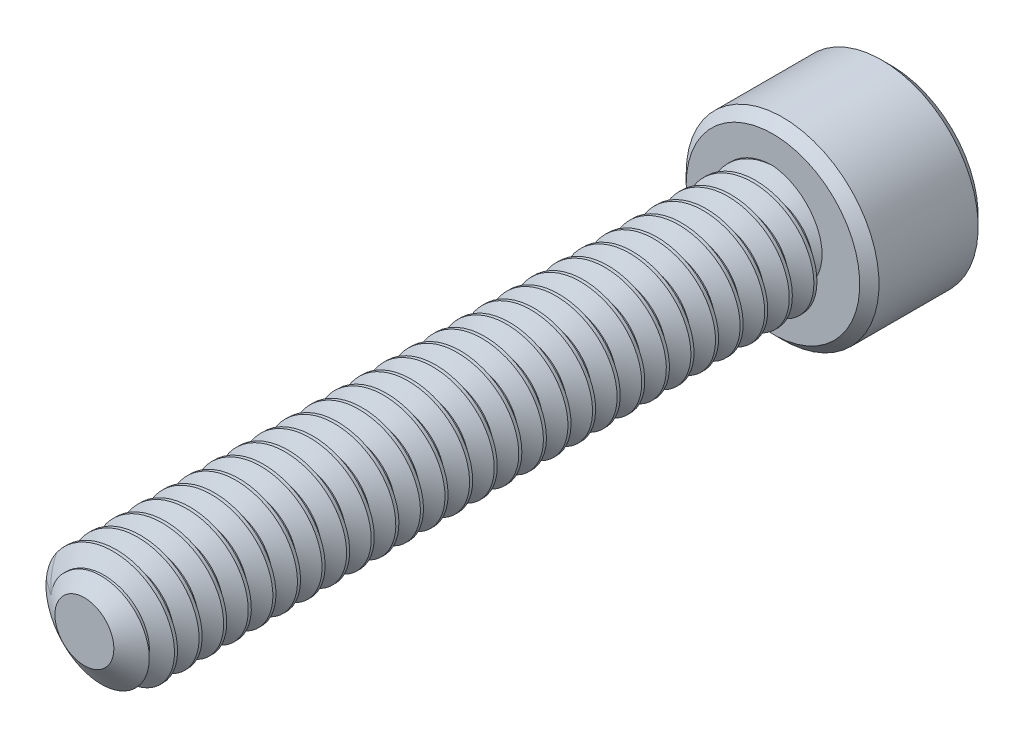
SolidWorks part; units mm, degrees
note: '?' marks a value the reader was unsure of.
other "DetailItem1"
ref_plane "Front Plane" through (0, 0, 0) normal (0, 0, 1) x (1, 0, 0)
ref_plane "Top Plane" through (0, 0, 0) normal (0, 1, 0) x (1, 0, 0)
ref_plane "Right Plane" through (0, 0, 0) normal (1, 0, 0) x (0, 0, -1)
sketch "Sketch1" plane through (0, 0, 0) normal (0, 0, 1) x (1, 0, 0)
  circle A0 centre (0, 0) radius 1.0922
  dimension "OD" = 2.1844
extrude "Extrude1" add sketch "Sketch1" against normal blind 12.7
sketch "Sketch2" plane through (0, 0, 0) normal (0, 0, 1) x (1, 0, 0)
  circle A0 centre (0, 0) radius 1.0922 construction
  circle A1 centre (0, 0) radius 1.0922
curve "Helix/Spiral1" pitch 0.4536 height 13.1536 turns 29 parameters "pitch"=0.4536
sketch "Sketch3" plane through (0, 0, 0) normal (1, 0, 0) x (0, 0, -1)
  line L0 (-0.3969, 1.0922) -> (-0.2268, 0.7976)
  line L1 (-0.2268, 0.7976) -> (-0.1701, 0.7976)
  line L2 (-0.1701, 0.7976) -> (0, 1.0922)
  line L3 (-0.3969, 1.0922) -> (0, 1.0922)
  line L4 (-0.1984, 1.0922) -> (-0.1984, 0.7976) construction
  line L5 (-0.3118, 0.9449) -> (-0.085, 0.9449) construction
  line L6 (0, 1.0922) -> (0, -1.0922) construction
  dimension "D1" = 0.0567
  dimension "D2" = 0.2268
  dimension "D3" = 60
sweep "Cut-Sweep1" cut profiles "Sketch3" path "Helix/Spiral1" align with end faces yes
sketch "Sketch4" plane through (0, 0, 0) normal (1, 0, 0) x (0, 0, -1)
  line L0 (0.3841, 1.0922) -> (0, 0.5436)
  line L1 (0, 0.5436) -> (0, 1.0922)
  line L2 (0.3841, 1.0922) -> (0, 1.0922)
  line L3 (-0.3969, 1.0922) -> (0, 1.0922) construction
  line L4 (0, 0) -> (7.0209, 0) construction
  dimension "D1" = 55
  dimension "D2" = 0.254
revolve "Cut-Revolve1" cut sketch "Sketch4" angle 360 about L4
sketch "Sketch6" plane through (0, 0, -12.7) normal (0, 0, -1) x (-1, 0, 0)
  circle A0 centre (0, 0) radius 1.778
  dimension "head dia" = 3.556
extrude "Extrude2" add sketch "Sketch6" along normal blind 2.1844
sketch "Sketch7" plane through (0, 0, -14.8844) normal (0, 0, -1) x (-1, 0, 0)
  line L1 (0, 1.1457) -> (-0.9922, 0.5728)
  line L2 (-0.9922, 0.5728) -> (-0.9922, -0.5728)
  line L3 (-0.9922, -0.5728) -> (0, -1.1457)
  line L4 (0, -1.1457) -> (0.9922, -0.5728)
  line L5 (0.9922, -0.5728) -> (0.9922, 0.5728)
  line L6 (0.9922, 0.5728) -> (0, 1.1457)
  circle A0 centre (0, 0) radius 0.9922 construction
  dimension "hex dia" = 1.9844
extrude "Cut-Extrude1" cut sketch "Sketch7" against normal blind 1.4883
sketch "Sketch8" plane through (0, 0, -14.8844) normal (0, 0, -1) x (-1, 0, 0)
  circle A0 centre (0, 0) radius 1.1457
extrude "Cut-Extrude2" cut sketch "Sketch8" against normal through all draft 45
chamfer "Chamfer1" distance 0.1778 angle 45 2 edges at (-1.778, 0, -14.8844) (-1.778, 0, -12.7)
sketch "Sketch10" plane through (0, 0, -12.7) normal (0, 0, 1) x (1, 0, 0)
  circle A1 centre (0, 0) radius 1.0922
  circle A2 centre (0, 0) radius 1.0922
  dimension "D1" = 0
ref_plane "Plane1" through (0, 0, -38.1) normal (0, 0, 1) x (1, 0, 0)
extrude "partial thread" [suppressed] add sketch "Sketch10" along normal up to surface (12.7 mm away) separate body
chamfer "Chamfer2" [suppressed] distance 0.0437 angle 45
combine bodies "Combine1" [suppressed] operation type? add bodies to combine 107 108
sketch "Sketch9" plane through (0, 0, 0) normal (1, 0, 0) x (0, 0, -1)
  line L0 (0, 1.0922) -> (0, -1.0922) construction
  line L1 (1.1339, 1.0922) -> (1.1339, -1.0922) construction
  dimension "D1" = 1.1339
equation "\"D3@Helix/Spiral1\" = \"screw length@Extrude1\"+\"pitch@Helix/Spiral1\""
equation "\"D1@Sketch3\" = \"pitch@Helix/Spiral1\"*.125"
equation "\"D2@Sketch3\" = \"pitch@Helix/Spiral1\"*.5"
equation "\"D1@Cut-Extrude1\" = \"hex dia@Sketch7\"*.75"
equation "\"D1@Chamfer1\" = \"head dia@Sketch6\"*.05"
equation "\"D1@Sketch9\" = \"pitch@Helix/Spiral1\"*2.5"
equation "\"D1@Chamfer2\"=\"OD@Sketch1\"*.02"
